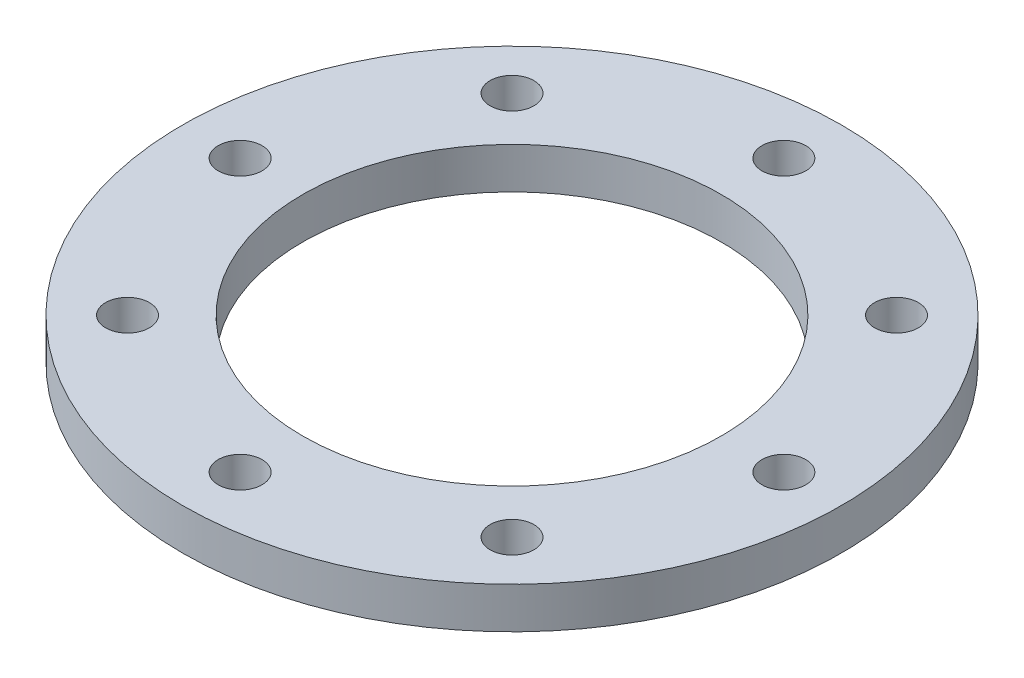
SolidWorks part; units mm, degrees
material "Plain Carbon Steel"
ref_plane "Front Plane" through (0, 0, 0) normal (0, 0, 1) x (1, 0, 0)
ref_plane "Top Plane" through (0, 0, 0) normal (0, 1, 0) x (1, 0, 0)
ref_plane "Right Plane" through (0, 0, 0) normal (1, 0, 0) x (0, 0, -1)
sketch "Sketch1" plane through (0, 0, 0) normal (0, 1, 0) x (1, 0, 0)
  circle A0 centre (0, 0) radius 50.8
  circle A1 centre (0, 0) radius 32.258
  dimension "D1" = 101.6
  dimension "D2" = 64.516
extrude "Boss-Extrude1" add sketch "Sketch1" along normal blind 6.35
hole_wizard "1/4 Clearance Hole1" positions "Sketch2" profile "Sketch3" hole size "1/4" standard "ANSI Inch" end condition through all
sketch "Sketch2" plane through (0, 6.35, 0) normal (0, 1, 0) x (1, 0, 0)
  point P0 (0, 41.91)
  dimension "D1" = 41.91
sketch "Sketch3" plane through (0, 6.35, -41.91) normal (1, 0, 0) x (0, 0, 1)
  line L0 (0, 0) -> (0, 6.35)
  line L1 (0, 6.35) -> (3.3782, 6.35)
  line L2 (3.3782, 6.35) -> (3.3782, 0)
  line L5 (3.3782, 0) -> (0, 0)
  line L11 (0, -6.35) -> (0, 107.95) construction
  dimension "Thru Hole Dia." = 6.7564
  dimension "Thru Hole Depth" = 6.35
pattern_circular "CirPattern1" count 8 over 360 about axis through (0, 6.35, 0) along (0, -1, 0) of "1/4 Clearance Hole1"
